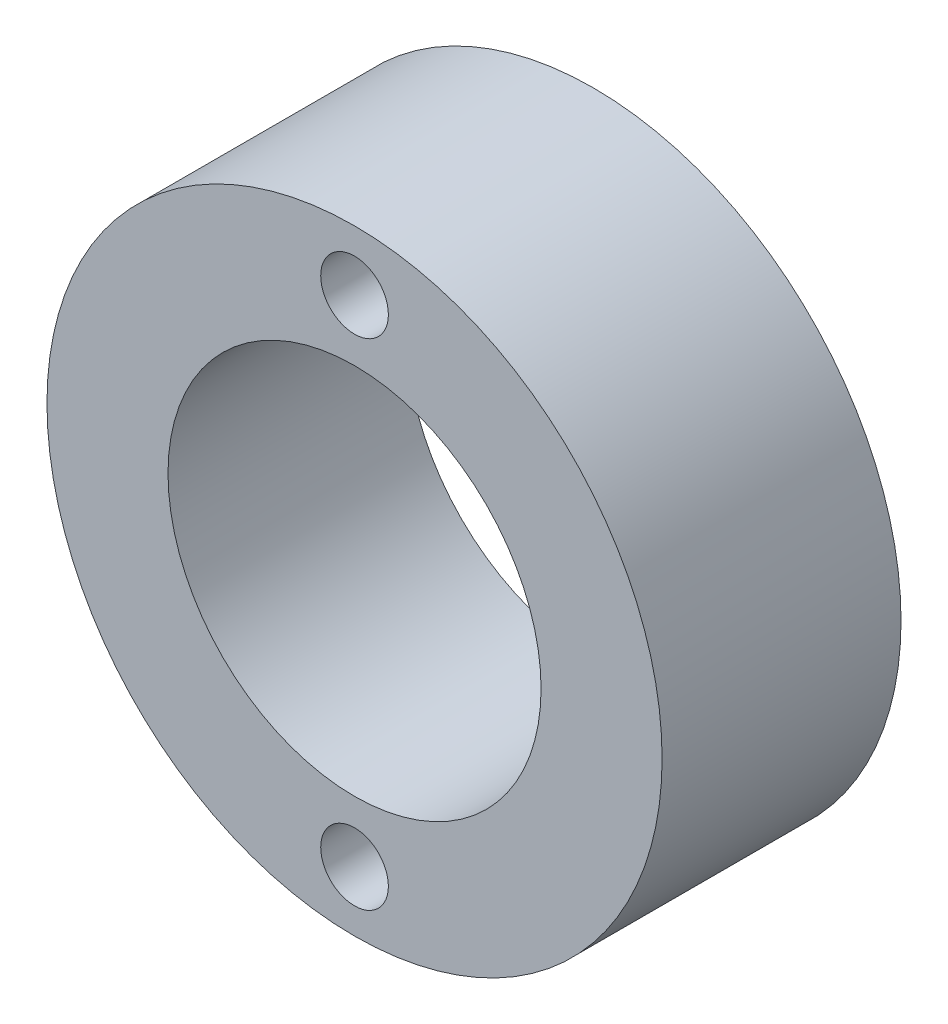
SolidWorks part; units mm, degrees
ref_plane "Front Plane" through (0, 0, 0) normal (0, 0, 1) x (1, 0, 0)
ref_plane "Top Plane" through (0, 0, 0) normal (0, 1, 0) x (1, 0, 0)
ref_plane "Right Plane" through (0, 0, 0) normal (1, 0, 0) x (0, 0, -1)
sketch "Sketch1" plane through (0, 0, 0) normal (0, 0, 1) x (1, 0, 0)
  line L1 (-1.9027, 18.097) -> (1.9027, 18.097) construction
  line L4 (0, 0) -> (0, 18.097) construction
  line L5 (0, 18.097) -> (0, 19.7034) construction
  line L6 (0, 19.101) -> (1.9973, 18.9963) construction
  line L7 (1.9973, 18.9963) -> (2.8966, 18.9017) construction
  line L8 (1.9973, 18.9963) -> (1.9027, 18.097) construction
  line L9 (-1.9973, 18.9963) -> (-1.9027, 18.097) construction
  line L10 (-1.9707, 18.7437) -> (-2.31, 21.971)
  line L11 (-2.31, 21.971) -> (2.31, 21.971)
  line L12 (2.31, 21.971) -> (1.9707, 18.7437)
  circle A0 centre (0, 0) radius 19.101 construction
  circle A1 centre (0, 0) radius 21.971 construction
  circle A2 centre (0, 0) radius 18.847 construction
  arc A3 (-0.4989, 18.4088) -> (0.4989, 18.4088) centre (0, 18.652) ccw
  arc A4 (-0.4989, 18.4088) -> (-0.5897, 18.7039) centre (0.4, 18.847) cw
  arc A5 (-1.9707, 18.7437) -> (-0.7441, 18.8323) centre (0, 0) cw
  arc A6 (-0.5897, 18.7039) -> (-0.7441, 18.8323) centre (-0.7382, 18.6824) ccw
  arc A7 (1.9707, 18.7437) -> (0.7441, 18.8323) centre (0, 0) ccw
  arc A8 (0.5897, 18.7039) -> (0.7441, 18.8323) centre (0.7382, 18.6824) cw
  arc A9 (0.4989, 18.4088) -> (0.5897, 18.7039) centre (-0.4, 18.847) ccw
  point P6 (0, 20.9083)
  point P11 (0, 19.101)
  point P13 (0, 21.971)
  point P14 (0, 18.847)
  dimension "D1" = 1.2049
  dimension "D2" = 0.6024
sketch "Sketch2" plane through (0, 0, 0) normal (1, 0, 0) x (0, 0, -1)
  line L0 (-9.1313, 3.175) -> (9.1313, 3.175)
  line L1 (-9.1313, 3.175) -> (-9.1313, 15.52)
  line L2 (-9.1313, 15.52) -> (-1.2787, 15.52)
  line L3 (-1.2787, 15.52) -> (-1.2787, 21.971)
  line L4 (-1.2787, 21.971) -> (0.2413, 21.971) construction
  line L5 (0.2413, 21.971) -> (0.2413, 18.847) construction
  line L6 (0.2413, 18.847) -> (7.6113, 18.847)
  line L7 (7.6113, 18.847) -> (7.6113, 21.971) construction
  line L8 (7.6113, 21.971) -> (9.1313, 21.971) construction
  line L9 (9.1313, 21.971) -> (9.1313, 3.175)
  line L10 (-9.1313, 0) -> (9.1313, 0) construction
  line L11 (8.3713, 21.971) -> (7.6113, 20.409)
  line L12 (0.2413, 20.409) -> (-0.5187, 21.971)
  line L13 (-1.2787, 21.971) -> (-0.5187, 21.971)
  line L14 (0.2413, 20.409) -> (0.2413, 18.847)
  line L15 (7.6113, 18.847) -> (7.6113, 20.409)
  line L16 (8.3713, 21.971) -> (9.1313, 21.971)
  arc A0 (0.2413, 20.409) -> (-0.5187, 21.971) centre (-1.7439, 20.409) ccw construction
  arc A1 (7.6113, 20.409) -> (8.3713, 21.971) centre (9.5965, 20.409) cw construction
  point P12 (0.2413, 20.409)
  point P14 (-0.5187, 21.971)
  point P20 (7.6113, 20.409)
  point P21 (8.3713, 21.971)
  point P25 (7.6113, 0)
  point P26 (0.2413, 0)
revolve "Revolve1" add sketch "Sketch2" angle 360 mid plane about L10
sketch "Sketch3" plane through (0, 0, 0) normal (0, 0, 1) x (1, 0, 0)
  line L6 (2.31, 21.971) -> (-2.31, 21.971)
  line L7 (1.9707, 18.7437) -> (2.31, 21.971)
  line L8 (-2.31, 21.971) -> (-1.9707, 18.7437)
  line L9 (2.31, 21.971) -> (-2.31, 21.971)
  line L10 (1.9707, 18.7437) -> (2.31, 21.971)
  line L11 (-2.31, 21.971) -> (-1.9707, 18.7437)
  arc A8 (1.9707, 18.7437) -> (0.7441, 18.8323) centre (0, 0) ccw
  arc A9 (0.7441, 18.8323) -> (0.5897, 18.7039) centre (0.7382, 18.6824) ccw
  arc A10 (0.4989, 18.4088) -> (0.5897, 18.7039) centre (-0.4, 18.847) ccw
  arc A11 (-0.4989, 18.4088) -> (0.4989, 18.4088) centre (0, 18.652) ccw
  arc A12 (-0.5897, 18.7039) -> (-0.4989, 18.4088) centre (0.4, 18.847) ccw
  arc A13 (-0.5897, 18.7039) -> (-0.7441, 18.8323) centre (-0.7382, 18.6824) ccw
  arc A14 (-0.7441, 18.8323) -> (-1.9707, 18.7437) centre (0, 0) ccw
  arc A15 (1.9707, 18.7437) -> (0.7441, 18.8323) centre (0, 0) ccw
  arc A16 (0.7441, 18.8323) -> (0.5897, 18.7039) centre (0.7382, 18.6824) ccw
  arc A17 (0.4989, 18.4088) -> (0.5897, 18.7039) centre (-0.4, 18.847) ccw
  arc A18 (-0.4989, 18.4088) -> (0.4989, 18.4088) centre (0, 18.652) ccw
  arc A19 (-0.5897, 18.7039) -> (-0.4989, 18.4088) centre (0.4, 18.847) ccw
  arc A20 (-0.5897, 18.7039) -> (-0.7441, 18.8323) centre (-0.7382, 18.6824) ccw
  arc A21 (-0.7441, 18.8323) -> (-1.9707, 18.7437) centre (0, 0) ccw
  dimension "D1" = 0
extrude "Cut-Extrude1" cut sketch "Sketch3" against normal up to vertex (7.6113 mm away) from vertex up to point (0, 18.847, -7.6113) starting at point (0, 18.847, -0.2413)
pattern_circular "CirPattern1" count 60 over 360 about axis through (0, 0, 9.1313) along (0, 0, 1) of "Cut-Extrude1"
sketch "Sketch4" plane through (0, 0, 0) normal (1, 0, 0) x (0, -1, 0)
  line L0 (0, -1.2787) -> (0, -9.1313) construction
  line L1 (-15.52, -1.2787) -> (15.52, -1.2787) construction
  line L2 (-15.52, -9.1313) -> (15.52, -9.1313) construction
  circle A0 centre (0, -5.205) radius 1.7526
extrude "Cut-Extrude2" cut sketch "Sketch4" along normal through all
ref_plane "Plane1" through (0, 0, 5.205) normal (0, 0, 1) x (1, 0, 0)
sketch "Sketch5" plane through (0, 0, 5.205) normal (0, 0, 1) x (1, 0, 0)
  line L0 (0, 0.1664) -> (0, 15.52) construction
  line L1 (3.175, -1.3716) -> (3.175, 0)
  line L2 (3.556, -1.7526) -> (15.0397, -1.7526)
  line L3 (3.175, 0) -> (15.52, 0) construction
  line L4 (3.175, 0) -> (15.4207, 0)
  line L5 (15.4207, 0) -> (15.4207, -1.3716)
  line L6 (3.556, -1.7526) -> (3.175, -1.3716)
  line L7 (15.4207, -1.3716) -> (15.0397, -1.7526)
  circle A0 centre (0, 0) radius 15.52 construction
  circle A1 centre (0, 0) radius 3.175 construction
  point P2 (3.175, -1.7526)
  point P11 (15.4207, -1.7526)
revolve "Revolve2" add sketch "Sketch5" angle 360 mid plane about L4
sketch "Sketch6" plane through (15.4207, 5.3841, 0) normal (-1, 0, 0) x (0, -1, 0)
  line L1 (5.3841, 6.2169) -> (4.5078, 5.7109)
  line L2 (4.5078, 5.7109) -> (4.5078, 4.6991)
  line L3 (4.5078, 4.6991) -> (5.3841, 4.1931)
  line L4 (5.3841, 4.1931) -> (6.2604, 4.6991)
  line L5 (6.2604, 4.6991) -> (6.2604, 5.7109)
  line L6 (6.2604, 5.7109) -> (5.3841, 6.2169)
  circle A0 centre (5.3841, 5.205) radius 0.8763 construction
  dimension "D1" = 1.7526
extrude "Cut-Extrude3" cut sketch "Sketch6" along normal blind 1.3144
pattern_circular "CirPattern2" count 2 over 90 about axis through (0, 0, 9.1313) along (0, 0, 1) of "Cut-Extrude2", "Revolve2", "Cut-Extrude3"
chamfer "Chamfer1" distance 0.776 angle 45 2 edges at (3.175, 0, 9.1313) (15.52, 0, 9.1313)
ref_axis "Center Axis 1" through (0, 0, -9.1313) along (0, 0, 1)
ref_plane "Contact Plane 1" through (0, 0, 9.1313) normal (0, 0, 1) x (1, 0, 0)
ref_plane "Contact Plane 2" through (0, 0, -9.1313) normal (0, 0, -1) x (-1, 0, 0)
sketch "Sketch7" plane through (0, 0, 0) normal (0, 1, 0) x (1, 0, 0)
  line L0 (-21.971, -1.2787) -> (21.971, -1.2787) construction
  line L1 (-21.971, -1.2787) -> (25.9937, -1.2787)
  line L2 (-21.971, -1.2787) -> (-21.971, -11.9749)
  line L3 (-21.971, -11.9749) -> (25.9937, -11.9749)
  line L4 (25.9937, -1.2787) -> (25.9937, -11.9749)
extrude "Cut-Extrude4" cut sketch "Sketch7" against normal through all both and the other way through all
sketch "Sketch8" plane through (0, 0, -9.1313) normal (0, 0, -1) x (-1, 0, 0)
  line L0 (9.5368, 0) -> (-9.934, 0) construction
  circle A0 centre (0, -15) radius 2.05
  circle A2 centre (0, 15) radius 2.05
  dimension "D3" = 4.1
  dimension "D1" = 15
extrude "Cut-Extrude5" cut sketch "Sketch8" against normal up to surface (10.41 mm away)
sketch "Sketch9" plane through (0, 0, 0) normal (0, 1, 0) x (1, 0, 0)
  line L0 (-21.971, 9.1313) -> (-21.971, -1.2787) construction
  line L1 (-21.971, -1.2787) -> (21.971, -1.2787) construction
  circle A0 centre (0, 3.9263) radius 1.8415
  point P8 (-21.971, 3.9263)
  dimension "D1" = 3.683
extrude "Cut-Extrude6" cut sketch "Sketch9" along normal through all
sketch "Sketch10" plane through (0, 0, 1.2787) normal (0, 0, 1) x (1, 0, 0)
  circle A0 centre (0, 0) radius 11.303
  dimension "D1" = 22.606
extrude "Cut-Extrude7" cut sketch "Sketch10" against normal blind 7.239
sketch "Sketch11" plane through (0, 0, 1.2787) normal (0, 0, 1) x (1, 0, 0)
  line L0 (0, 0) -> (0, 17.05) construction
  circle A0 centre (0, 0) radius 18.6375
  circle A1 centre (0, 0) radius 11.303 construction
  circle A2 centre (0, 0) radius 11.303
  circle A3 centre (0, 15) radius 2.05 construction
  circle A4 centre (0, 15) radius 2.05
  circle A5 centre (0, -15) radius 2.05 construction
  circle A6 centre (0, -15) radius 2.05
  circle A8 centre (0, 0) radius 17.05 construction
  dimension "D1" = 1.5875
extrude "Boss-Extrude1" add sketch "Sketch11" along normal blind 14.478
sketch "Sketch12" plane through (0, 0, 0) normal (0, 1, 0) x (1, 0, 0)
  line L1 (-21.971, -1.2787) -> (18.6375, -1.2787)
  line L2 (-21.971, -1.2787) -> (-21.971, -15.7567)
  line L3 (-21.971, -15.7567) -> (18.6375, -15.7567)
  line L4 (18.6375, -1.2787) -> (18.6375, -15.7567)
  line L5 (21.971, -1.2787) -> (18.6375, -1.2787)
  line L6 (21.971, -1.2787) -> (21.971, -15.7567)
  line L7 (21.971, -15.7567) -> (18.6375, -15.7567)
  line L8 (18.6375, -1.2787) -> (18.6375, -15.7567)
  line L9 (-21.971, -1.2787) -> (21.971, -1.2787)
  line L10 (-21.971, -1.2787) -> (-21.971, 9.1313)
  line L11 (-21.971, 9.1313) -> (21.971, 9.1313)
  line L12 (21.971, -1.2787) -> (21.971, 9.1313)
extrude "Cut-Extrude8" cut sketch "Sketch12" against normal through all both and the other way through all contours L5 L12 L11 L10 L1 region at (0, 0, -3.9263)
equation "\"D2@Sketch1\" = \"D1@Sketch1\"/2"
equation "\"D1@Sketch6\" = \"Set Screw@Sketch4\" / 2"
equation "\"D1@Cut-Extrude3\" = \"D1@Sketch6\"*.75"
equation "\"D1@Chamfer1\"=\"Hub Dia@Sketch2\"*.025"
